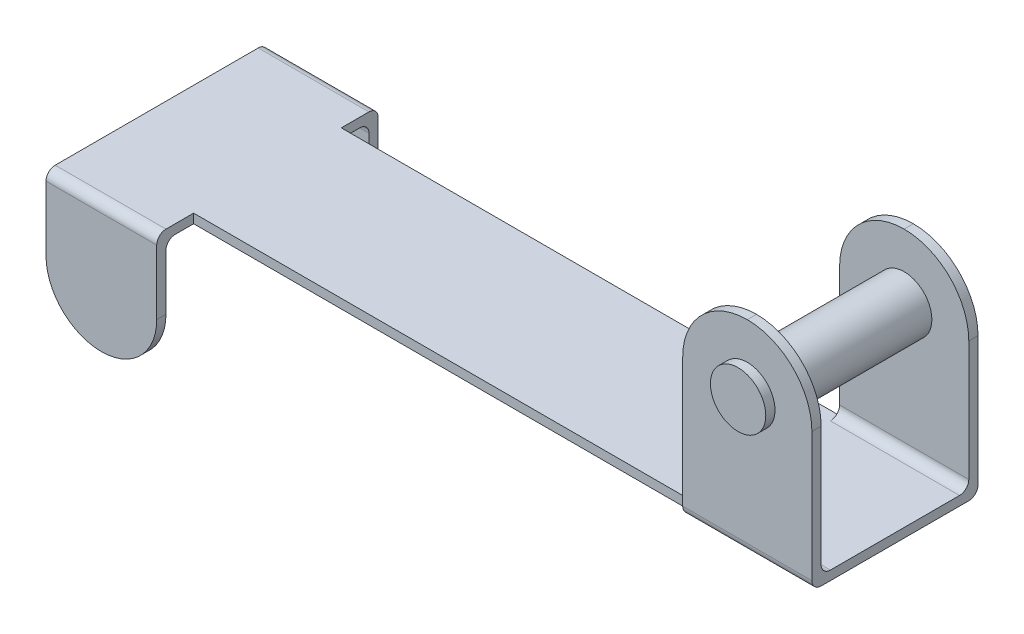
SolidWorks part; units mm, degrees
ref_plane "Front Plane" through (0, 0, 0) normal (0, 0, 1) x (1, 0, 0)
ref_plane "Top Plane" through (0, 0, 0) normal (0, 1, 0) x (1, 0, 0)
ref_plane "Right Plane" through (0, 0, 0) normal (1, 0, 0) x (0, 0, -1)
sketch "Sketch1" plane through (0, 0, 0) normal (0, 0, 1) x (1, 0, 0)
  line L1 (10, -0.125) -> (-10, -0.125)
  line L2 (10, -0.125) -> (10, 0.125)
  line L3 (10, 0.125) -> (-10, 0.125)
  line L4 (-10, -0.125) -> (-10, 0.125)
  line L5 (10, -0.125) -> (-10, 0.125) construction
  line L6 (10, 0.125) -> (-10, -0.125) construction
  point P0 (0, 0)
  dimension "D1" = 0.25
  dimension "D2" = 20
extrude "Boss-Extrude1" add sketch "Sketch1" along normal mid plane 4
sketch "Sketch2" plane through (10, 0, 0) normal (1, 0, 0) x (0, 0, -1)
  line L0 (-2, 0.125) -> (-2, -0.125) construction
  line L1 (-2, -0.125) -> (-2.25, -0.125)
  line L2 (-2, -0.125) -> (-2, 5.375)
  line L3 (-2, 5.375) -> (-2.25, 5.375)
  line L4 (-2.25, -0.125) -> (-2.25, 5.375)
  line L5 (2, -0.125) -> (2.25, -0.125)
  line L6 (2, -0.125) -> (2, 5.375)
  line L7 (2, 5.375) -> (2.25, 5.375)
  line L8 (2.25, -0.125) -> (2.25, 5.375)
  dimension "D1" = 5.5
extrude "Boss-Extrude2" add sketch "Sketch2" against normal blind 3.5
fillet "Fillet1" radius 0.25 4 edges at (8.25, -0.125, -2.25) (8.25, -0.125, 2.25) (8.25, 0.125, -2) (8.25, 0.125, 2)
fillet "Fillet2" radius 1.75 4 edges at (10, 5.375, -2.125) (6.5, 5.375, -2.125) (6.5, 5.375, 2.125) (10, 5.375, 2.125)
sketch "Sketch3" plane through (0, 0, 2.25) normal (0, 0, 1) x (1, 0, 0)
  circle A0 centre (8.25, 3.625) radius 0.75
  dimension "D1" = 1.5
extrude "Boss-Extrude3" add sketch "Sketch3" along normal mid plane 5 from surface starting at plane "Front Plane"
sketch "Sketch5" plane through (-10, 0, 0) normal (-1, 0, 0) x (0, 0, 1)
  line L0 (-2, -0.125) -> (-2.75, -0.125)
  line L1 (-2.75, -0.125) -> (-2.75, -3.375)
  line L2 (-2.75, -3.375) -> (-3, -3.375)
  line L3 (-3, -3.375) -> (-3, 0.125)
  line L4 (-3, 0.125) -> (-2, 0.125)
  line L5 (-2, 0.125) -> (-2, -0.125)
  line L6 (0, 0) -> (0, -1.7008) construction
  line L7 (3, 0.125) -> (2, 0.125)
  line L8 (3, -3.375) -> (3, 0.125)
  line L9 (2.75, -3.375) -> (3, -3.375)
  line L10 (2.75, -0.125) -> (2.75, -3.375)
  line L11 (2, -0.125) -> (2.75, -0.125)
  line L12 (2, 0.125) -> (2, -0.125)
  dimension "D1" = 3.5
  dimension "D2" = 0.75
extrude "Boss-Extrude5" add sketch "Sketch5" against normal blind 3
fillet "Fillet3" radius 1.5 4 edges at (-10, -3.375, 2.875) (-7, -3.375, 2.875) (-7, -3.375, -2.875) (-10, -3.375, -2.875)
fillet "Fillet4" radius 0.25 4 edges at (-8.5, 0.125, 3) (-8.5, -0.125, 2.75) (-8.5, 0.125, -3) (-8.5, -0.125, -2.75)
